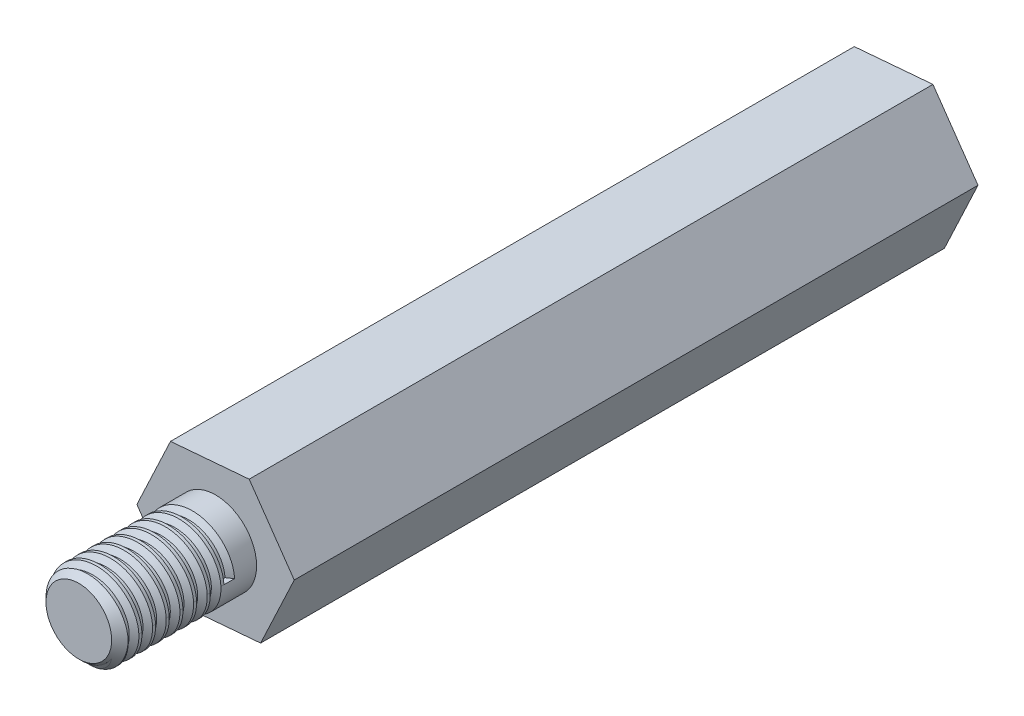
SolidWorks part; units mm, degrees
ref_plane "前视基准面" through (0, 0, 0) normal (0, 0, 1) x (1, 0, 0)
ref_plane "上视基准面" through (0, 0, 0) normal (0, 1, 0) x (1, 0, 0)
ref_plane "右视基准面" through (0, 0, 0) normal (1, 0, 0) x (0, 0, -1)
sketch "草图1" plane through (0, 0, 0) normal (0, 0, 1) x (1, 0, 0)
  line L1 (1.6473, -2.3706) -> (2.8766, 0.2414)
  line L2 (2.8766, 0.2414) -> (1.2293, 2.6119)
  line L3 (1.2293, 2.6119) -> (-1.6473, 2.3706)
  line L4 (-1.6473, 2.3706) -> (-2.8766, -0.2414)
  line L5 (-2.8766, -0.2414) -> (-1.2293, -2.6119)
  line L6 (-1.2293, -2.6119) -> (1.6473, -2.3706)
  circle A0 centre (0, 0) radius 1.5
  circle A1 centre (0, 0) radius 2.5 construction
  dimension "D1" = 3
  dimension "D2" = 5
extrude "凸台-拉伸1" add sketch "草图1" along normal blind 25 contours L5 L6 L1 L2 L3 L4 A0 | A0 region at (0.2025, -2.4138, 0)
hole_wizard "M3 螺纹孔1" positions "3D草图1" profile "草图2" tap size "M3" standard "GB"
sketch3d "3D草图1"
  point P0 (0, 0, 0)
  point P3 (0, 0, 0)
  point P5 (0, 0, 0)
  point P7 (0, 0, 0)
  point P9 (0, 0, 0)
sketch "草图2" plane through (0, 0, 0) normal (1, 0, 0) x (0, 1, 0)
  line L0 (0, 0) -> (0, 15.7511)
  line L1 (0, 15.7511) -> (1.25, 15)
  line L2 (1.25, 15) -> (1.25, 0)
  line L5 (1.25, 0) -> (0, 0)
  line L10 (0, 15.7511) -> (-1.25, 15) construction
  line L11 (0, -6.35) -> (0, 107.95) construction
  dimension "螺纹孔钻头直径" = 2.5
  dimension "螺纹孔钻头深度" = 15
  dimension "导头角度" = 118
cosmetic thread "孔螺蚊线1" parameters "D1"=10, "D2"=3
cosmetic thread "孔螺蚊线2" parameters "D1"=10, "D2"=3
cosmetic thread "孔螺蚊线3" parameters "D1"=10, "D2"=3
cosmetic thread "孔螺蚊线4" parameters "D1"=10, "D2"=3
cosmetic thread "孔螺蚊线5" parameters "D1"=10, "D2"=3
sketch "草图3" plane through (0, 0, 25) normal (0, 0, 1) x (1, 0, 0)
  circle A0 centre (0, 0) radius 1.5
  dimension "D1" = 3
extrude "凸台-拉伸2" add sketch "草图3" along normal blind 5
chamfer "倒角1" distance 0.3 angle 45 1 edges at (1.5, 0, 30)
sketch "草图4" plane through (0, 0, 30) normal (0, 0, 1) x (1, 0, 0)
  circle A0 centre (0, 0) radius 1.5 construction
  circle A1 centre (0, 0) radius 1.5
curve "螺旋线/涡状线1" pitch 0.5 height 4 radius 1.5 centre (0, 0, 30) axis (0, 0, -1) start towards (1, 0, 0)
sketch "草图5" plane through (0, 0, 0) normal (0, 1, 0) x (1, 0, 0)
  line L0 (1.5432, -30.225) -> (1.5432, -29.775)
  line L1 (1.5432, -29.775) -> (1.2932, -29.95)
  line L2 (1.2932, -29.95) -> (1.2932, -30.05)
  line L3 (1.2932, -30.05) -> (1.5432, -30.225)
  line L4 (1.2932, -30) -> (1.5984, -30) construction
  line L7 (-1.2, -30) -> (1.2, -30) construction
  line L8 (-1.2, -30) -> (1.2, -30) construction
  dimension "D1" = 0.45
  dimension "D2" = 0.1
  dimension "D3" = 0.25
sweep "切除-扫描2" cut profiles "草图5" path "螺旋线/涡状线1"
